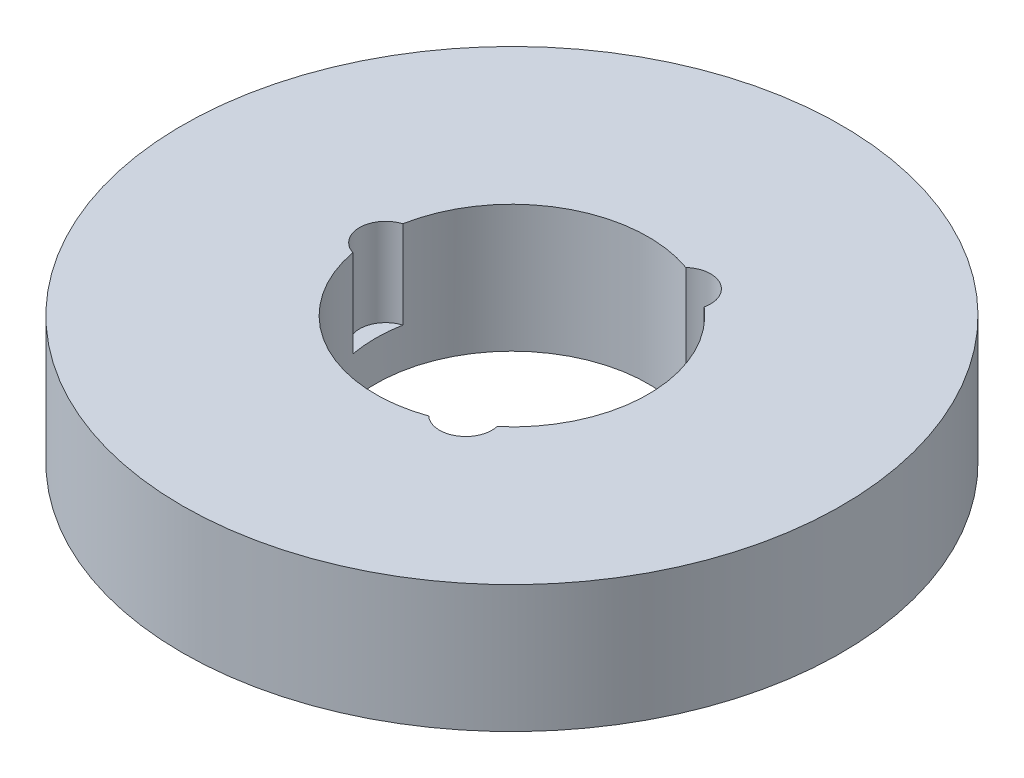
SolidWorks part; units mm, degrees
ref_plane "Front Plane" through (0, 0, 0) normal (0, 0, 1) x (1, 0, 0)
ref_plane "Top Plane" through (0, 0, 0) normal (0, 1, 0) x (1, 0, 0)
ref_plane "Right Plane" through (0, 0, 0) normal (1, 0, 0) x (0, 0, -1)
sketch "Sketch1" plane through (0, 0, 0) normal (0, 1, 0) x (1, 0, 0)
  circle A0 centre (0, 0) radius 72.5
  dimension "FLANGE_OD" = 145
extrude "Boss-Extrude1" add sketch "Sketch1" along normal blind 28
sketch "Sketch2" plane through (0, 0, 0) normal (0, 1, 0) x (1, 0, 0)
  circle A0 centre (0, 0) radius 30
  dimension "BORE_D" = 60
extrude "Cut-Extrude1" cut sketch "Sketch2" along normal through all
sketch "Sketch3" plane through (0, 28, 0) normal (0, 1, 0) x (1, 0, 0)
  circle A0 centre (0, 0) radius 27.7726 construction
  circle A1 centre (-27.7726, 0) radius 5.7616
  dimension "BOLT_D" = 11.5231
  dimension "BOLT_PCD" = 55.5453
extrude "Cut-Extrude2" cut sketch "Sketch3" against normal blind 19.3102
pattern_circular "CirPattern1" count 3 over 360 about axis through (0, 0, 0) along (0, 1, 0) of "Cut-Extrude2"
